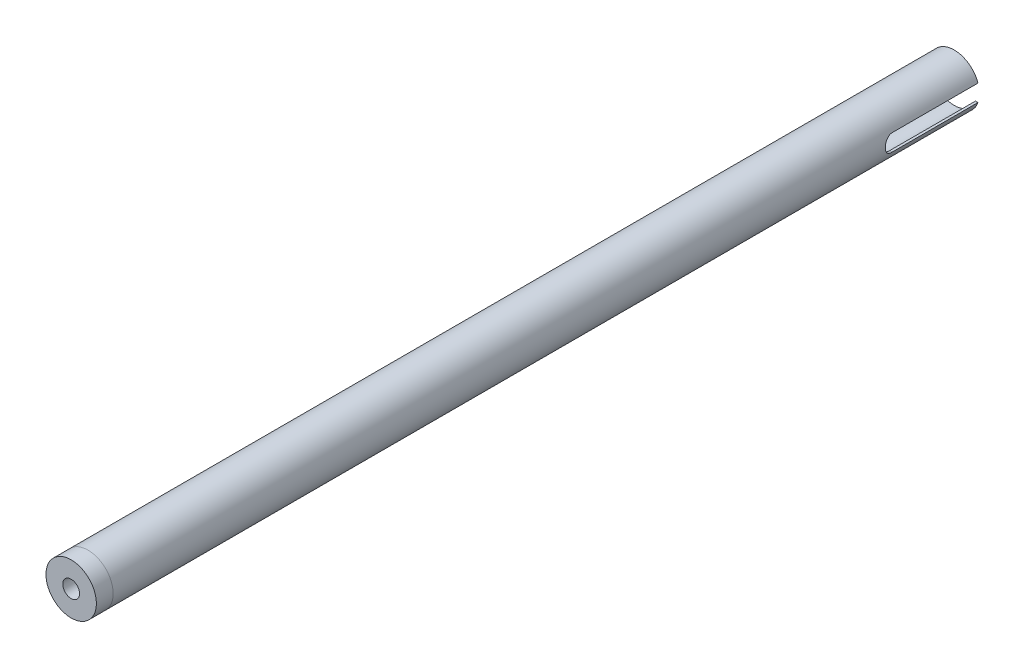
SolidWorks part; units mm, degrees
material "AISI 4130 Steel, normalized at 870C"
ref_plane "Front Plane" through (0, 0, 0) normal (0, 0, 1) x (1, 0, 0)
ref_plane "Top Plane" through (0, 0, 0) normal (0, 1, 0) x (1, 0, 0)
ref_plane "Right Plane" through (0, 0, 0) normal (1, 0, 0) x (0, 0, -1)
sketch "Axis" plane through (0, 0, 0) normal (0, 1, 0) x (1, 0, 0)
  line L0 (0, 0) -> (0, 333.5734) construction
  line L1 (0, 0) -> (0, -21.9075) construction
  line L2 (0, 333.5734) -> (-9.525, 333.5734) construction
  line L4 (0, 368.0751) -> (-10.3188, 330.6983) construction
  dimension "D1" = 21.9075
  dimension "D2" = 9.525
sketch "Sketch1" plane through (0, 0, 0) normal (0, 0, 1) x (1, 0, 0)
  line L0 (-9.525, 0) -> (9.525, 0) construction
  line L1 (-8.9803, 3.175) -> (8.9803, 3.175)
  line L2 (-8.9803, -3.175) -> (8.9803, -3.175)
  circle A0 centre (0, 0) radius 9.525
  circle A1 centre (0, 0) radius 8.636
  circle A2 centre (0, 0) radius 3.175
  dimension "D1" = 19.05
  dimension "D3" = 6.35
  dimension "D2" = 0.889
  dimension "D4" = 6.35
extrude "Threaded insert 1-1" add sketch "Sketch1" against normal blind 6.35 contours A2 L1 A1 | A1 L1 A0 | A2 L0 A1 L1 | A1 L0 A0 L1 | L0 A1 L2 A0 | L0 A2 L2 A1 | A2 L2 A1 | A1 L2 A0 | L0 A1 L2 A2 | L0 A0 L2 A1 | A0 L0 A1 L1 | A1 L0 A2 L1 region at (5.4259, 1.6615, 0) region at (5.4259, -1.6615, 0) region at (8.8881, 1.6046, 0) region at (8.8881, -1.6046, 0) region at (-5.4259, -1.6615, 0) region at (-5.4259, 1.6615, 0) region at (0, 5.4321, 0) region at (0, -5.4321, 0) region at (0, 8.8265, 0) region at (8.5057, -3.3655, 0) region at (-8.8881, -1.6046, 0) region at (-8.8881, 1.6046, 0)
extrude "Threaded insert 1-2" add sketch "Sketch1<3>" against normal blind 6.35 from surface contours A2 L1 A1 | A2 L0 A1 L1 | L0 A2 L2 A1 | A2 L2 A1 | L0 A1 L2 A2 | A1 L0 A2 L1 region at (5.4259, 1.6615, 0) region at (5.4259, -1.6615, 0) region at (-5.4259, -1.6615, 0) region at (-5.4259, 1.6615, 0) region at (0, 5.4321, 0) region at (0, -5.4321, 0) starting at face at (9.525, 0, -6.35)
sketch "Sketch1<3>" plane through (0, 0, 0) normal (0, 0, 1) x (1, 0, 0) same geometry as "Sketch1"
extrude "A-arm tube" add sketch "Sketch1<4>" against normal up to vertex (333.5734 mm away) from surface separate body contours A1 L1 A0 | A1 L0 A0 L1 | L0 A1 L2 A0 | A1 L2 A0 | L0 A0 L2 A1 | A0 L0 A1 L1 region at (8.8881, 1.6046, 0) region at (8.8881, -1.6046, 0) region at (0, 8.8265, 0) region at (8.5057, -3.3655, 0) region at (-8.8881, -1.6046, 0) region at (-8.8881, 1.6046, 0) up to point (0, 0, -333.5734) starting at face at (8.636, 0, -6.35)
sketch "Sketch1<4>" plane through (0, 0, 0) normal (0, 0, 1) x (1, 0, 0) same geometry as "Sketch1"
extrude "Apex slot" cut sketch "Sketch1<5>" along normal blind 35.56 from surface contours A0 L0 A1 L1 | L0 A0 L2 A1 | A1 L0 A0 L1 | L0 A1 L2 A0 region at (8.8881, 1.6046, 0) region at (8.8881, -1.6046, 0) region at (-8.8881, -1.6046, 0) region at (-8.8881, 1.6046, 0) starting at face at (8.636, 0, -333.5734)
sketch "Sketch1<5>" plane through (0, 0, 0) normal (0, 0, 1) x (1, 0, 0) same geometry as "Sketch1"
fillet "Fillet1" radius 3.175 4 edges at (-8.5057, 3.175, -298.0134) (-8.5057, -3.175, -298.0134) (8.5057, -3.175, -298.0134) (8.5057, 3.175, -298.0134)
equation "\"tube diameter\"= 3 / 4"
equation "\"tube thickness\"= .035"
equation "\"apex thickness\"= .25"
equation "\"tube slot\"= 1.4"
equation "\"D1@Sketch1\"=\"tube diameter\""
equation "\"D2@Sketch1\"=\"tube thickness\""
equation "\"threaded insert hole\"= 1 / 4"
equation "\"D3@Sketch1\"=\"threaded insert hole\""
equation "\"D4@Sketch1\"=\"apex thickness\""
equation "\"D1@Apex slot\" = \"tube slot\""
equation "\"D1@Fillet1\"=\"apex thickness\"/2"
equation "\"D2@Axis\"=\"tube diameter\"/2"
